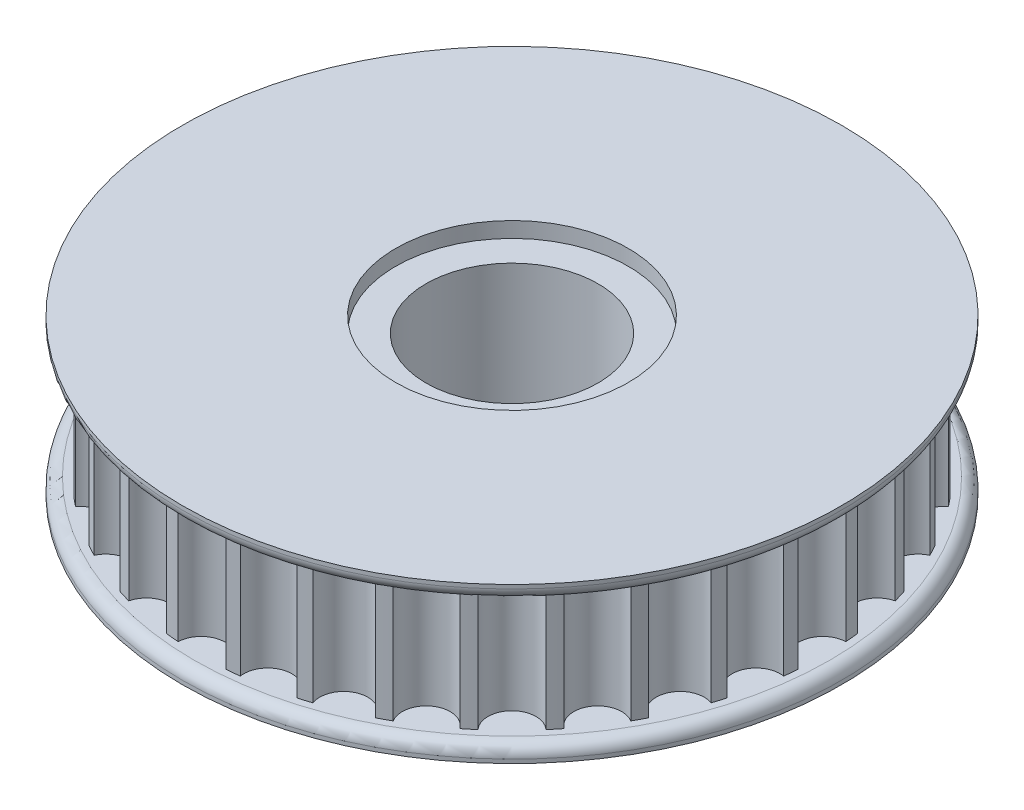
SolidWorks part; units mm, degrees
ref_plane "Front Plane" through (0, 0, 0) normal (0, 0, 1) x (1, 0, 0)
ref_plane "Top Plane" through (0, 0, 0) normal (0, 1, 0) x (1, 0, 0)
ref_plane "Right Plane" through (0, 0, 0) normal (1, 0, 0) x (0, 0, -1)
sketch "Sketch1" plane through (0, 0, 0) normal (0, 1, 0) x (1, 0, 0)
  line L0 (0, -55) -> (0, 55) construction
  circle A0 centre (0, 0) radius 40.08
  arc A1 (-3.0977, 39.9601) -> (3.0977, 39.9601) centre (0, 40.08) ccw
  arc A2 (4.7577, 39.7966) -> (10.834, 38.588) centre (7.8192, 39.3099) ccw
  arc A3 (12.4302, 38.1038) -> (18.154, 35.7329) centre (15.338, 37.0291) ccw
  arc A4 (19.625, 34.9466) -> (24.7763, 31.5046) centre (22.2673, 33.3253) ccw
  arc A5 (26.0657, 30.4465) -> (30.4465, 26.0657) centre (28.3408, 28.3408) ccw
  arc A6 (31.5046, 24.7763) -> (34.9466, 19.625) centre (33.3253, 22.2673) ccw
  arc A7 (35.7329, 18.154) -> (38.1038, 12.4302) centre (37.0291, 15.338) ccw
  arc A8 (38.588, 10.834) -> (39.7966, 4.7577) centre (39.3099, 7.8192) ccw
  arc A9 (39.9601, 3.0977) -> (39.9601, -3.0977) centre (40.08, 0) ccw
  arc A10 (39.7966, -4.7577) -> (38.588, -10.834) centre (39.3099, -7.8192) ccw
  arc A11 (38.1038, -12.4302) -> (35.7329, -18.154) centre (37.0291, -15.338) ccw
  arc A12 (34.9466, -19.625) -> (31.5046, -24.7763) centre (33.3253, -22.2673) ccw
  arc A13 (30.4465, -26.0657) -> (26.0657, -30.4465) centre (28.3408, -28.3408) ccw
  arc A14 (24.7763, -31.5046) -> (19.625, -34.9466) centre (22.2673, -33.3253) ccw
  arc A15 (18.154, -35.7329) -> (12.4302, -38.1038) centre (15.338, -37.0291) ccw
  arc A16 (10.834, -38.588) -> (4.7577, -39.7966) centre (7.8192, -39.3099) ccw
  arc A17 (3.0977, -39.9601) -> (-3.0977, -39.9601) centre (0, -40.08) ccw
  arc A18 (-4.7577, -39.7966) -> (-10.834, -38.588) centre (-7.8192, -39.3099) ccw
  arc A19 (-12.4302, -38.1038) -> (-18.154, -35.7329) centre (-15.338, -37.0291) ccw
  arc A20 (-19.625, -34.9466) -> (-24.7763, -31.5046) centre (-22.2673, -33.3253) ccw
  arc A21 (-26.0657, -30.4465) -> (-30.4465, -26.0657) centre (-28.3408, -28.3408) ccw
  arc A22 (-31.5046, -24.7763) -> (-34.9466, -19.625) centre (-33.3253, -22.2673) ccw
  arc A23 (-35.7329, -18.154) -> (-38.1038, -12.4302) centre (-37.0291, -15.338) ccw
  arc A24 (-38.588, -10.834) -> (-39.7966, -4.7577) centre (-39.3099, -7.8192) ccw
  arc A25 (-39.9601, -3.0977) -> (-39.9601, 3.0977) centre (-40.08, 0) ccw
  arc A26 (-39.7966, 4.7577) -> (-38.588, 10.834) centre (-39.3099, 7.8192) ccw
  arc A27 (-38.1038, 12.4302) -> (-35.7329, 18.154) centre (-37.0291, 15.338) ccw
  arc A28 (-34.9466, 19.625) -> (-31.5046, 24.7763) centre (-33.3253, 22.2673) ccw
  arc A29 (-30.4465, 26.0657) -> (-26.0657, 30.4465) centre (-28.3408, 28.3408) ccw
  arc A30 (-24.7763, 31.5046) -> (-19.625, 34.9466) centre (-22.2673, 33.3253) ccw
  arc A31 (-18.154, 35.7329) -> (-12.4302, 38.1038) centre (-15.338, 37.0291) ccw
  arc A32 (-10.834, 38.588) -> (-4.7577, 39.7966) centre (-7.8192, 39.3099) ccw
  circle A33 centre (0, 0) radius 11.1
  point P10 (0, 36.98)
  point P99 (0, 0)
  dimension "D1" = 3.1
  dimension "D2" = 32
  dimension "D4" = 22.2
  dimension "D3" = 80.16
extrude "Boss-Extrude1" add sketch "Sketch1" along normal mid plane 16 contours A32 A0 A31 A30 A29 A28 A27 A26 A25 A24 A23 A22 A21 A20 A19 A18 A17 A16 A15 A14 A13 A12 A11 A10 A9 A8 A7 region at (35.8498, 0, 0)
sketch "Sketch2" plane through (0, 8, 0) normal (0, 1, 0) x (1, 0, 0)
  circle A0 centre (0, 0) radius 15
  circle A1 centre (0, 0) radius 42.5
  dimension "D1" = 30
  dimension "D2" = 85
extrude "Boss-Extrude2" add sketch "Sketch2" along normal blind 2
mirror "Mirror1" about plane through (0, 0, 0) normal (0, 1, 0) of "Boss-Extrude2"
fillet "Fillet1" radius 1.5 2 edges at (0, 8, 42.5) (0, -8, 42.5)
